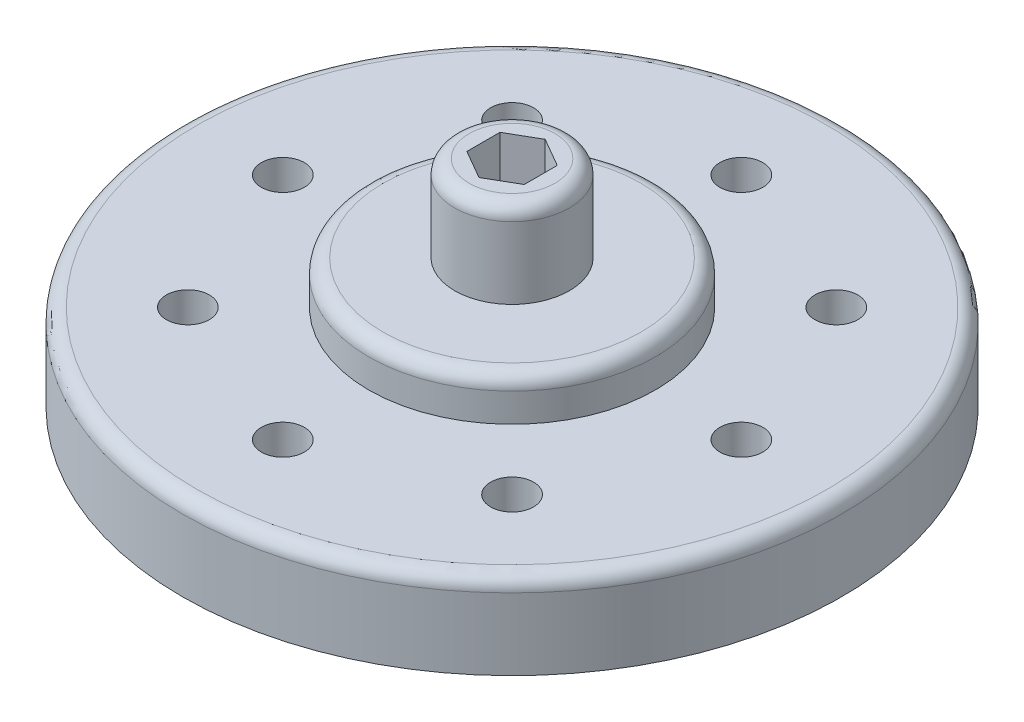
SolidWorks part; units mm, degrees
material "Comercialmente puro CP-Ti UNS R50400 (SS)"
ref_plane "Alzado" through (0, 0, 0) normal (0, 0, 1) x (1, 0, 0)
ref_plane "Planta" through (0, 0, 0) normal (0, 1, 0) x (1, 0, 0)
ref_plane "Vista lateral" through (0, 0, 0) normal (1, 0, 0) x (0, 0, -1)
sketch "Croquis1" plane through (0, 0, 0) normal (0, 1, 0) x (1, 0, 0)
  line L0 (-17.8, 0) -> (17.8, 0) construction
  line L1 (-17.8, -22.5) -> (17.8, -22.5) construction
  line L2 (17.8, -17.3) -> (17.8, 17.3)
  line L3 (11.8, 25.3) -> (-11.8, 25.3)
  line L4 (-17.8, -17.3) -> (-17.8, 17.3)
  line L5 (0, 25.3) -> (0, -25.3) construction
  line L6 (15, 25.3) -> (15, -22.1056) construction
  line L7 (-11.8, 25.3) -> (11.8, 25.3)
  line L8 (-12.2, 23.8) -> (-12.2, -18.2)
  line L9 (-10.7, -19.7) -> (10.7, -19.7)
  line L10 (12.2, 23.8) -> (12.2, -18.2)
  line L11 (12.2, 19.8) -> (17.8, 19.8)
  line L12 (17.4641, 18.4094) -> (13.4641, 24.4094)
  line L13 (1, 13.8774) -> (0, 14.4547)
  line L14 (0, 14.4547) -> (-1, 13.8774)
  line L15 (-1, 13.8774) -> (-1, 12.7226)
  line L16 (-1, 12.7226) -> (0, 12.1453)
  line L17 (0, 12.1453) -> (1, 12.7226)
  line L18 (1, 12.7226) -> (1, 13.8774)
  line L19 (-17.4641, 18.4094) -> (-13.4641, 24.4094)
  line L20 (17.4641, -18.4094) -> (13.4641, -24.4094)
  line L21 (-17.4641, -18.4094) -> (-13.4641, -24.4094)
  line L22 (-11.8, -25.3) -> (11.8, -25.3)
  line L23 (-10.7, 25.3) -> (10.7, 25.3)
  line L24 (12.2, 15.8) -> (17.8, 15.8)
  circle A0 centre (0, 13.3) radius 11.5
  circle A1 centre (0, 13.3) radius 2
  circle A2 centre (0, 13.3) radius 8 construction
  circle A4 centre (0, 13.3) radius 5
  circle A5 centre (0, 21.3) radius 0.75
  circle A7 centre (15, 17.8) radius 1
  circle A8 centre (15, 0.8) radius 1
  circle A9 centre (15, -16.2) radius 1
  circle A10 centre (-8.5, -22.5) radius 1
  circle A11 centre (8.5, -22.5) radius 1
  circle A12 centre (-15, -16.2) radius 1
  circle A13 centre (-15, 0.8) radius 1
  circle A14 centre (-15, 17.8) radius 1
  circle A15 centre (0, 13.3) radius 1 construction
  arc A16 (13.4641, 24.4094) -> (11.8, 25.3) centre (11.8, 23.3) ccw
  arc A17 (17.4641, 18.4094) -> (17.8, 17.3) centre (15.8, 17.3) cw
  arc A18 (-17.4641, 18.4094) -> (-17.8, 17.3) centre (-15.8, 17.3) ccw
  arc A19 (-13.4641, 24.4094) -> (-11.8, 25.3) centre (-11.8, 23.3) cw
  arc A20 (13.4641, -24.4094) -> (11.8, -25.3) centre (11.8, -23.3) cw
  arc A21 (17.4641, -18.4094) -> (17.8, -17.3) centre (15.8, -17.3) ccw
  arc A22 (-13.4641, -24.4094) -> (-11.8, -25.3) centre (-11.8, -23.3) ccw
  arc A23 (-17.4641, -18.4094) -> (-17.8, -17.3) centre (-15.8, -17.3) cw
  arc A24 (10.7, -19.7) -> (12.2, -18.2) centre (10.7, -18.2) ccw
  arc A25 (-12.2, -18.2) -> (-10.7, -19.7) centre (-10.7, -18.2) ccw
  arc A26 (-12.2, 23.8) -> (-10.7, 25.3) centre (-10.7, 23.8) cw
  arc A27 (10.7, 25.3) -> (12.2, 23.8) centre (10.7, 23.8) cw
  point P1 (0, 25.3)
  point P4 (0, 25.3)
  point P56 (12.8704, 25.3)
  point P59 (17.8, 17.9056)
  dimension "D5" = 23
  dimension "D7" = 1.5
  dimension "D8" = 2
  dimension "D9" = 12.5
  dimension "D10" = 17
  dimension "D11" = 16
  dimension "D13" = 10
  dimension "D14" = 4
  dimension "D17" = 2
  dimension "D18" = 2
  dimension "D21" = 4
  dimension "D16" = 1.5
  dimension "D3" = 35.6
  dimension "D4" = 50.6
  dimension "D6" = 12
  dimension "D15" = 17
  dimension "D19" = 45
  dimension "D20" = 24.4
  dimension "D22" = 2
  dimension "D23" = 4
  dimension "D24" = 6
  dimension "D25" = 4.5
extrude "Saliente-Extruir1" add sketch "Croquis1" along normal blind 3 contours A0
extrude "Cortar-Extruir2" cut sketch "Croquis1<9>" along normal blind 3 contours A5
sketch "Croquis1<9>" plane through (0, 0, 0) normal (0, 1, 0) x (1, 0, 0) same geometry as "Croquis1"
pattern_circular "MatrizC2" count 8 over 360 about axis through (0, 3, -13.3) along (0, 1, 0) of "Cortar-Extruir2"
extrude "Saliente-Extruir2" add sketch "Croquis1<11>" along normal blind 1.5 from surface contours A4 starting at face at (7.25, 3, -13.3)
sketch "Croquis1<11>" plane through (0, 0, 0) normal (0, 1, 0) x (1, 0, 0) same geometry as "Croquis1"
extrude "Saliente-Extruir3" add sketch "Croquis1<12>" along normal blind 3 from surface contours A1 L18 L17 L16 L15 L14 L13 region at (-1.9434, 0, -13.3) starting at face at (0, 4.5, -8.3)
sketch "Croquis1<12>" plane through (0, 0, 0) normal (0, 1, 0) x (1, 0, 0) same geometry as "Croquis1"
fillet "Redondeo1" radius 0.5 3 edges at (0, 7.5, -11.3) (0, 4.5, -8.3) (0, 3, -1.8)
extrude "Saliente-Extruir4" add sketch "Croquis1<13>" against normal blind 1 contours A4 A1 region at (-4.8586, 0, -13.3)
sketch "Croquis1<13>" plane through (0, 0, 0) normal (0, 1, 0) x (1, 0, 0) same geometry as "Croquis1"
